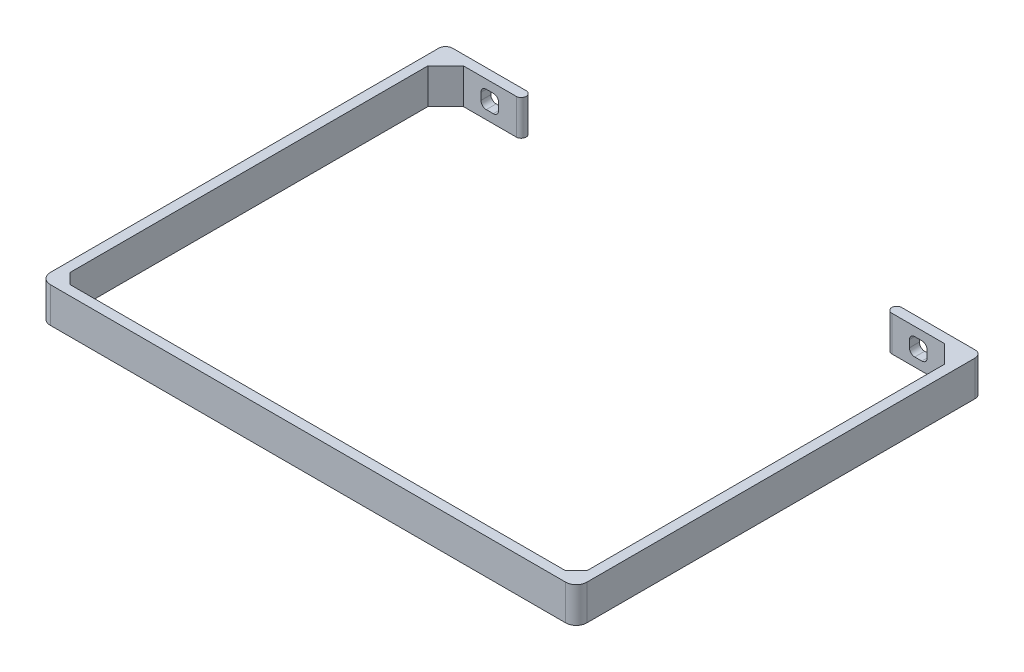
SolidWorks part; units mm, degrees
ref_plane "Plano frontal" through (0, 0, 0) normal (0, 0, 1) x (1, 0, 0)
ref_plane "Plano superior" through (0, 0, 0) normal (0, 1, 0) x (1, 0, 0)
ref_plane "Plano direito" through (0, 0, 0) normal (1, 0, 0) x (0, 0, -1)
sketch "Esboço1" plane through (0, 0, 0) normal (0, 1, 0) x (1, 0, 0)
  line L0 (-73.2, 54.7) -> (73.2, 54.7)
  line L1 (-76, 57.5) -> (76, 57.5)
  line L2 (-76, 57.5) -> (-76, -57.5)
  line L3 (-76, -57.5) -> (76, -57.5)
  line L4 (76, 57.5) -> (76, -57.5)
  line L5 (-76, 57.5) -> (76, -57.5) construction
  line L6 (-76, -57.5) -> (76, 57.5) construction
  line L7 (73.2, 54.7) -> (73.2, -54.7)
  line L8 (-73.2, -54.7) -> (73.2, -54.7)
  line L9 (-73.2, 54.7) -> (-73.2, -54.7)
  point P0 (0, 0)
  dimension "D1" = 152
  dimension "D2" = 115
  dimension "D3" = 2.8
extrude "Paredes" add sketch "Esboço1" along normal blind 10
fillet "Filete1" radius 3 1 edges at (76, 5, 57.5) type face fillet first side face at (0, 5, 57.5) second side face at (76, 5, 0)
fillet "Filete2" radius 3 1 edges at (-76, 5, 57.5) type face fillet first side face at (-76, 5, 0) second side face at (-1.5, 5, 57.5)
fillet "Filete3" radius 2 1 edges at (76, 5, -57.5) type face fillet first side face at (0, 5, -57.5) second side face at (76, 5, -1.5)
fillet "Filete4" radius 2 1 edges at (-76, 5, -57.5) type face fillet first side face at (-76, 5, -1.5) second side face at (-1, 5, -57.5)
chamfer "Chanfro1" distance 3 angle 45 1 edges at (73.2, 5, 54.7)
chamfer "Chanfro2" distance 3 angle 45 1 edges at (-73.2, 5, 54.7)
chamfer "Chanfro3" distance 5 angle 45 1 edges at (-73.2, 5, -54.7)
chamfer "Chanfro4" distance 5 angle 45 1 edges at (73.2, 5, -54.7)
sketch "Esboço3" plane through (0, 0, -57.5) normal (0, 0, -1) x (-1, 0, 0)
  line L0 (0, 13.6983) -> (0, -5.421) construction
  line L1 (-86.9025, 5) -> (73.4973, 5) construction
  line L2 (63.2, 6) -> (63.2, 4)
  line L3 (-61.7, 7.5) -> (-59.7, 7.5)
  line L4 (-63.2, 6) -> (-63.2, 4)
  line L5 (-61.7, 2.5) -> (-59.7, 2.5)
  line L6 (-58.2, 6) -> (-58.2, 4)
  line L7 (-63.2, 7.5) -> (-58.2, 2.5) construction
  line L8 (-63.2, 2.5) -> (-58.2, 7.5) construction
  line L9 (61.7, 2.5) -> (59.7, 2.5)
  line L10 (58.2, 6) -> (58.2, 4)
  line L11 (61.7, 7.5) -> (59.7, 7.5)
  line L12 (-74, 0) -> (74, 0) construction
  line L13 (-51.8, 10) -> (51.8, 10)
  line L14 (-51.8, 10) -> (-51.8, 0)
  line L15 (-51.8, 0) -> (51.8, 0)
  line L16 (51.8, 10) -> (51.8, 0)
  line L17 (-51.8, 10) -> (51.8, 0) construction
  line L18 (-51.8, 0) -> (51.8, 10) construction
  arc A0 (-61.7, 2.5) -> (-63.2, 4) centre (-61.7, 4) cw
  arc A1 (-59.7, 2.5) -> (-58.2, 4) centre (-59.7, 4) ccw
  arc A2 (-58.2, 6) -> (-59.7, 7.5) centre (-59.7, 6) ccw
  arc A3 (-63.2, 6) -> (-61.7, 7.5) centre (-61.7, 6) cw
  arc A4 (61.7, 2.5) -> (63.2, 4) centre (61.7, 4) ccw
  arc A5 (59.7, 2.5) -> (58.2, 4) centre (59.7, 4) cw
  arc A6 (58.2, 6) -> (59.7, 7.5) centre (59.7, 6) cw
  arc A7 (63.2, 6) -> (61.7, 7.5) centre (61.7, 6) ccw
  point P5 (-60.7, 5)
  point P34 (0, 5)
  dimension "D4" = 1.5
  dimension "D1" = 5
  dimension "D2" = 5
  dimension "D3" = 5
  dimension "D5" = 60.7
  dimension "D6" = 103.6
extrude "Cortes" cut sketch "Esboço3" against normal blind 10
fillet "Filete7" 2 edges at (51.8, 5, -57.5) (51.8, 5, -54.7) type full round first side face at (60.7, 5, -57.5) second side face at (60, 5, -54.7) middle face at (51.8, 5, -56.1)
fillet "Filete8" 2 edges at (-51.8, 5, -54.7) (-51.8, 5, -57.5) type full round first side face at (-60.7, 5, -54.7) second side face at (-60.7, 5, -57.5) middle face at (-51.8, 5, -56.1)
